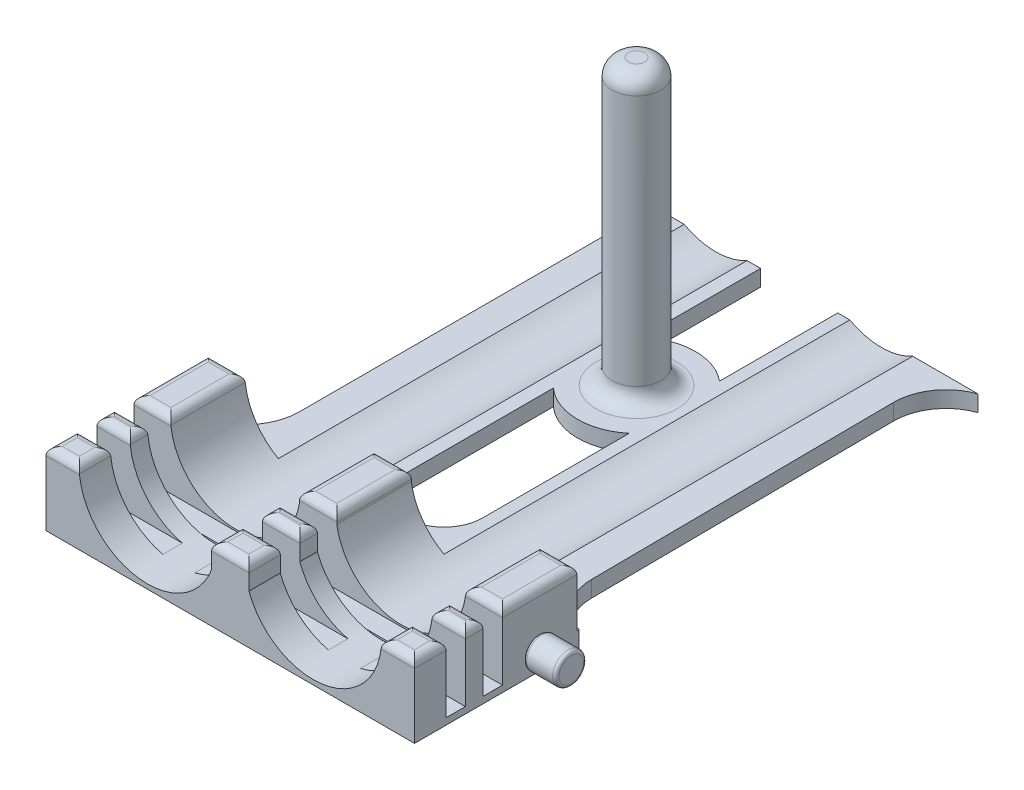
SolidWorks part; units mm, degrees
ref_plane "Front Plane" through (0, 0, 0) normal (0, 0, 1) x (1, 0, 0)
ref_plane "Top Plane" through (0, 0, 0) normal (0, 1, 0) x (1, 0, 0)
ref_plane "Right Plane" through (0, 0, 0) normal (1, 0, 0) x (0, 0, -1)
sketch "Sketch1" plane through (0, 0, 0) normal (0, 1, 0) x (1, 0, 0)
  line L1 (-12.5, -45) -> (12.5, -45)
  line L2 (-12.5, -45) -> (-12.5, 45)
  line L3 (-12.5, 45) -> (12.5, 45)
  line L4 (12.5, -45) -> (12.5, 45)
  line L5 (-12.5, -45) -> (12.5, 45) construction
  line L6 (-12.5, 45) -> (12.5, -45) construction
  point P0 (0, 0)
  dimension "D1" = 90
  dimension "D2" = 25
extrude "Boss-Extrude1" add sketch "Sketch1" along normal blind 9
sketch "Sketch4" plane through (0, 9, 0) normal (0, 1, 0) x (1, 0, 0)
  line L0 (0, 36.8) -> (0, -45) construction
  line L1 (0, 45) -> (0, -45) construction
  line L2 (-12.5, -45) -> (12.5, -45) construction
  line L3 (12.5, 45) -> (-12.5, 45) construction
  line L4 (0, 36.8) -> (-8, 36.8)
  line L5 (0, 36.8) -> (0, -34.2)
  line L6 (0, -34.2) -> (-8, -34.2)
  line L7 (-8, 36.8) -> (-8, -34.2)
  line L8 (0, 36.8) -> (-8, -34.2) construction
  line L9 (0, -34.2) -> (-8, 36.8) construction
  line L10 (-12.5, 0) -> (12.5, 0) construction
  line L11 (-12.5, 45) -> (-12.5, -45) construction
  line L12 (12.5, -45) -> (12.5, 45) construction
  point P9 (-4, 1.3)
  dimension "D1" = 71
  dimension "D2" = 8
revolve "Syringe Body slot" cut sketch "Sketch4" angle 360 about L5
sketch "Sketch5" plane through (0, 9, 0) normal (0, 1, 0) x (1, 0, 0)
  line L0 (-13.75, -35.3671) -> (13.75, -35.3671) construction
  line L1 (8, -34.2) -> (-8, -34.2) construction
  line L2 (-12.5, 45) -> (-12.5, -45) construction
  line L3 (0, -34.2) -> (0, -35.3671) construction
  line L4 (12.5, -45) -> (12.5, 45) construction
  line L5 (-12.5, -36.5671) -> (12.5, -36.5671)
  line L6 (-12.5, -36.5671) -> (-12.5, -34.1671)
  line L7 (-12.5, -34.1671) -> (12.5, -34.1671)
  line L8 (12.5, -36.5671) -> (12.5, -34.1671)
  line L9 (-12.5, -36.5671) -> (12.5, -34.1671) construction
  line L10 (-12.5, -34.1671) -> (12.5, -36.5671) construction
  line L11 (-13.75, -39.9361) -> (13.75, -39.9361) construction
  line L12 (0, -38.7691) -> (0, -39.9361) construction
  line L13 (-14, -41.1361) -> (14, -41.1361)
  line L14 (-14, -41.1361) -> (-14, -38.7361)
  line L15 (-14, -38.7361) -> (14, -38.7361)
  line L16 (14, -41.1361) -> (14, -38.7361)
  line L17 (-14, -41.1361) -> (14, -38.7361) construction
  line L18 (-14, -38.7361) -> (14, -41.1361) construction
  point P6 (0, -35.3671)
  point P20 (0, -39.9361)
  dimension "D2" = 13.75
extrude "Flange Slot" cut sketch "Sketch5" against normal blind 8.2
sketch "Sketch6" plane through (0, 9, 0) normal (0, 1, 0) x (1, 0, 0)
  line L0 (0, -36.5671) -> (0, -45) construction
  line L1 (-12.5, -36.5671) -> (12.5, -36.5671) construction
  line L2 (-12.5, -45) -> (12.5, -45) construction
  line L4 (0, -45) -> (-8.4329, -45)
  line L5 (0, -45) -> (0, -36.5671)
  line L6 (0, -36.5671) -> (-8.4329, -36.5671)
  line L7 (-8.4329, -45) -> (-8.4329, -36.5671)
  line L8 (0, -45) -> (-8.4329, -36.5671) construction
  line L9 (0, -36.5671) -> (-8.4329, -45) construction
  point P9 (-4.2165, -40.7835)
revolve "Plunger Slot" cut sketch "Sketch6" angle 360 about L5
sketch "Sketch18" plane through (0, 9, 0) normal (0, 1, 0) x (1, 0, 0)
  line L1 (-12.5, -25) -> (12.5, -25)
  line L2 (-12.5, -25) -> (-12.5, 25)
  line L3 (-12.5, 25) -> (12.5, 25)
  line L4 (12.5, -25) -> (12.5, 25)
  line L5 (-12.5, -25) -> (12.5, 25) construction
  line L6 (-12.5, 25) -> (12.5, -25) construction
  point P0 (0, 0)
  dimension "D1" = 50
  dimension "D2" = 25
extrude "Syringe Bay" cut sketch "Sketch18" against normal blind 7
sketch "Sketch26" plane through (0, 9, 0) normal (0, 1, 0) x (1, 0, 0)
  line L0 (12.5, 25) -> (8, 25) construction
  line L1 (-19.8999, 25) -> (18.4526, 25)
  line L2 (-19.8999, 25) -> (-19.8999, 45.2156)
  line L3 (-19.8999, 45.2156) -> (18.4526, 45.2156)
  line L4 (18.4526, 25) -> (18.4526, 45.2156)
extrude "Cut-Extrude14" cut sketch "Sketch26" against normal blind 10
pattern_linear "LPattern3" count 2 spacing 20.4 along (1, 0, 0) of bodies 163
sketch "Sketch31" plane through (-12.5, 0, 0) normal (-1, 0, 0) x (0, 0, 1)
  line L0 (25, 9) -> (34.1671, 9) construction
  circle A0 centre (29.6873, 2.2313) radius 1.9
  dimension "D1" = 1.9
extrude "Cut-Extrude16" cut sketch "Sketch31" against normal blind 4
sketch "Sketch33" plane through (32.9, 0, 0) normal (1, 0, 0) x (0, 0, -1)
  circle A0 centre (-29.6873, 2.2313) radius 1.9
  dimension "D1" = 1.9
extrude "Boss-Extrude2" add sketch "Sketch33" along normal blind 4
fillet "Fillet1" radius 0.4 2 edges at (36.9, 2.2313, 27.7873) (32.9, 2.2313, 27.7873)
fillet "Fillet2" radius 0.6 2 edges at (-12.5, 2.2313, 31.5873) (-8.5, 2.2313, 31.5873)
sketch "Sketch35" plane through (0, 2, 0) normal (0, 1, 0) x (1, 0, 0)
  line L0 (-14, 25) -> (-14, -25) construction
  line L1 (-14, 0) -> (-14, -25) construction
  line L2 (-14, -12.5) -> (-14, 12.5) construction
  line L3 (-14, -12.5) -> (-14, -25) construction
  line L4 (-14, -25) -> (-14, -18.75) construction
  line L5 (-14, 25) -> (-14, 12.5) construction
  line L6 (-14, 18.75) -> (-14, -18.75) construction
  line L7 (-14, 18.75) -> (-14, -18.75) construction
  line L8 (-7.5725, 18.75) -> (-7.5725, -18.75)
  line L9 (-20.4275, 18.75) -> (-20.4275, -18.75)
  line L10 (10.2, 25) -> (10.4665, -45) construction
  line L12 (-12.5, 25) -> (32.9, 25) construction
  line L15 (8.4329, -45) -> (12.5, -45) construction
  line L18 (34.4469, 18.9344) -> (34.7324, -18.5645) construction
  line L23 (9.6592, -17.7945) -> (10.288, -2.3812) construction
  line L24 (10.288, 25.2845) -> (10.288, 12.1282) construction
  line L25 (10.288, 25.2845) -> (10.288, 12.1282) construction
  line L26 (15.038, 25.2845) -> (15.038, 10.4351)
  line L27 (5.538, 25.2845) -> (5.538, 10.2777)
  line L28 (-14, 0) -> (2.8875, 0) construction
  line L29 (9.6592, 0) -> (14.4092, 0) construction
  line L30 (28.0196, 18.8855) -> (28.3051, -18.6134)
  line L31 (10.288, -2.3812) -> (10.288, -18.75) construction
  line L32 (10.288, -2.3812) -> (10.288, -18.75) construction
  line L33 (40.8742, 18.9834) -> (41.1597, -18.5156)
  line L34 (15.038, -0.688) -> (15.038, -18.75)
  line L35 (5.538, -0.5306) -> (5.538, -18.75)
  line L36 (10.2, 25) -> (10.2, -35.6686) construction
  line L37 (34.4469, 18.9344) -> (34.7324, -18.5645) construction
  line L38 (34.3993, 25.1842) -> (34.4945, 12.6846) construction
  line L39 (34.78, -24.8143) -> (34.7324, -18.5645) construction
  line L40 (34.6848, -12.3147) -> (34.78, -24.8143) construction
  line L41 (34.6848, -12.3147) -> (34.4945, 12.6846) construction
  line L42 (34.5896, 0.185) -> (34.78, -24.8143) construction
  line L43 (34.3993, 25.1842) -> (34.78, -24.8143) construction
  arc A0 (-7.5725, 18.75) -> (-20.4275, 18.75) centre (-14, 18.75) ccw
  arc A1 (-20.4275, -18.75) -> (-7.5725, -18.75) centre (-14, -18.75) ccw
  arc A4 (15.038, 25.2845) -> (5.538, 25.2845) centre (10.288, 25.2845) ccw
  arc A5 (5.538, -18.75) -> (15.038, -18.75) centre (10.288, -18.75) ccw
  arc A6 (5.538, -0.5306) -> (15.038, -0.688) centre (10.3789, 4.8735) ccw
  arc A7 (15.038, 10.4351) -> (5.538, 10.2777) centre (10.3789, 4.8735) ccw
  arc A8 (28.0196, 18.8855) -> (40.8742, 18.9834) centre (34.4469, 18.9344) cw
  arc A9 (41.1597, -18.5156) -> (28.3051, -18.6134) centre (34.7324, -18.5645) cw
  point P9 (-14, 0)
  point P21 (34.5896, 0.185)
  point P36 (9.6592, 0)
  point P47 (0, 0)
  dimension "D1" = 25
extrude "Cut-Extrude17" cut sketch "Sketch35" against normal blind 10
combine bodies "Combine2" operation type add bodies to combine 176 175 175 169
sketch "Sketch36" plane through (0, 2, 0) normal (0, 1, 0) x (1, 0, 0)
  circle A0 centre (10.3789, 4.8735) radius 3
  dimension "D1" = 3
extrude "Boss-Extrude3" add sketch "Sketch36" along normal blind 35
fillet "Fillet5" radius 2 2 edges at (10.3789, 2, -7.8735) (10.3789, 37, -1.8735)
fillet "Fillet7" radius 1 36 edges at (30.8665, 9, 41.1361) (32.9, 9, 43.0681) (30.8665, 9, 45) (28.8329, 9, 43.0681) (7.9, 9, 43.0681) (10.2, 9, 41.1361) (12.5, 9, 43.0681) (10.2, 9, 45) (10.2, 9, 36.5671) (12.5, 9, 37.6516) (10.2, 9, 38.7361) (7.9, 9, 37.6516) (7.9, 9, 29.5835) (30.8665, 9, 36.5671) (32.9, 9, 37.6516) (30.8665, 9, 38.7361) (28.8329, 9, 37.6516) (32.9, 9, 29.5835) (30.65, 9, 34.1671) (28.4, 9, 29.5835) (30.65, 9, 25) (10.2, 9, 34.1671) (10.2, 9, 25) (12.5, 9, 29.5835) (-8, 9, 29.5835) (-10.25, 9, 34.1671) (-12.5, 9, 29.5835) (-10.25, 9, 25) (-10.4665, 9, 38.7361) (-12.5, 9, 37.6516) (-10.4665, 9, 36.5671) (-8.4329, 9, 37.6516) (-10.4665, 9, 45) (-12.5, 9, 43.0681) (-10.4665, 9, 41.1361) (-8.4329, 9, 43.0681)
